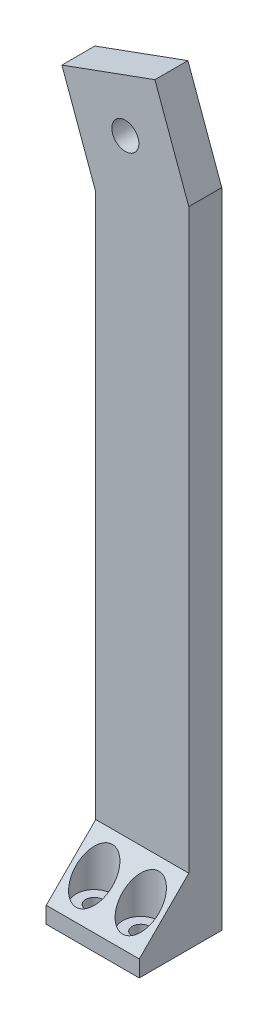
SolidWorks part; units mm, degrees
ref_plane "Front Plane" through (0, 0, 0) normal (0, 0, 1) x (1, 0, 0)
ref_plane "Top Plane" through (0, 0, 0) normal (0, 1, 0) x (1, 0, 0)
ref_plane "Right Plane" through (0, 0, 0) normal (1, 0, 0) x (0, 0, -1)
sketch "Sketch1" plane through (0, 0, 0) normal (0, 0, 1) x (1, 0, 0)
  line L0 (0, 0) -> (535.6248, 194.9515) construction
  line L1 (535.6248, 194.9515) -> (535.6248, 0)
  line L2 (535.6248, 194.9515) -> (525.3642, 223.1423)
  line L3 (525.3642, 223.1423) -> (-10.2606, 28.1908) construction
  line L4 (-10.2606, 28.1908) -> (0, 0) construction
  line L5 (530.4945, 209.0469) -> (516.3991, 203.9166) construction
  line L7 (507.434, 184.6909) -> (497.1734, 212.8817)
  line L8 (497.1734, 212.8817) -> (525.3642, 223.1423)
  line L9 (507.434, 184.6909) -> (507.434, 0)
  line L10 (507.434, 0) -> (535.6248, 0)
  circle A0 centre (516.3991, 203.9166) radius 4.1
extrude "Boss-Extrude1" add sketch "Sketch1" along normal blind 10
sketch "Sketch2" plane through (0, 0, 10) normal (0, 0, 1) x (1, 0, 0)
  line L0 (535.6248, 0) -> (535.6248, 194.9515) construction
  line L1 (507.434, 0) -> (535.6248, 0)
  line L2 (507.434, 0) -> (507.434, 5)
  line L3 (507.434, 5) -> (535.6248, 5)
  line L4 (535.6248, 0) -> (535.6248, 5)
extrude "Boss-Extrude2" add sketch "Sketch2" along normal blind 15
sketch "Sketch4" plane through (0, 5, 0) normal (0, 1, 0) x (1, 0, 0)
  line L0 (521.5294, -17.5) -> (535.6248, -17.5) construction
  line L1 (507.434, -25) -> (507.434, -10) construction
  line L3 (507.434, -17.5) -> (521.5294, -17.5) construction
  line L4 (535.6248, -25) -> (535.6248, -10) construction
  circle A0 centre (528.5771, -17.5) radius 2.6
  circle A1 centre (514.4817, -17.5) radius 2.6
extrude "Cut-Extrude1" cut sketch "Sketch4" against normal blind 20
ref_plane "Plane1" through (0, 5, 0) normal (0, 1, 0) x (1, 0, 0)
chamfer "Chamfer1" distance 15 angle 45 1 edges at (521.5294, 5, 10)
sketch "Sketch5" plane through (0, 5, 0) normal (0, 1, 0) x (1, 0, 0)
  circle A0 centre (514.4817, -17.5) radius 5.5
  circle A1 centre (528.5771, -17.5) radius 5.5
extrude "Cut-Extrude2" cut sketch "Sketch5" along normal blind 20
